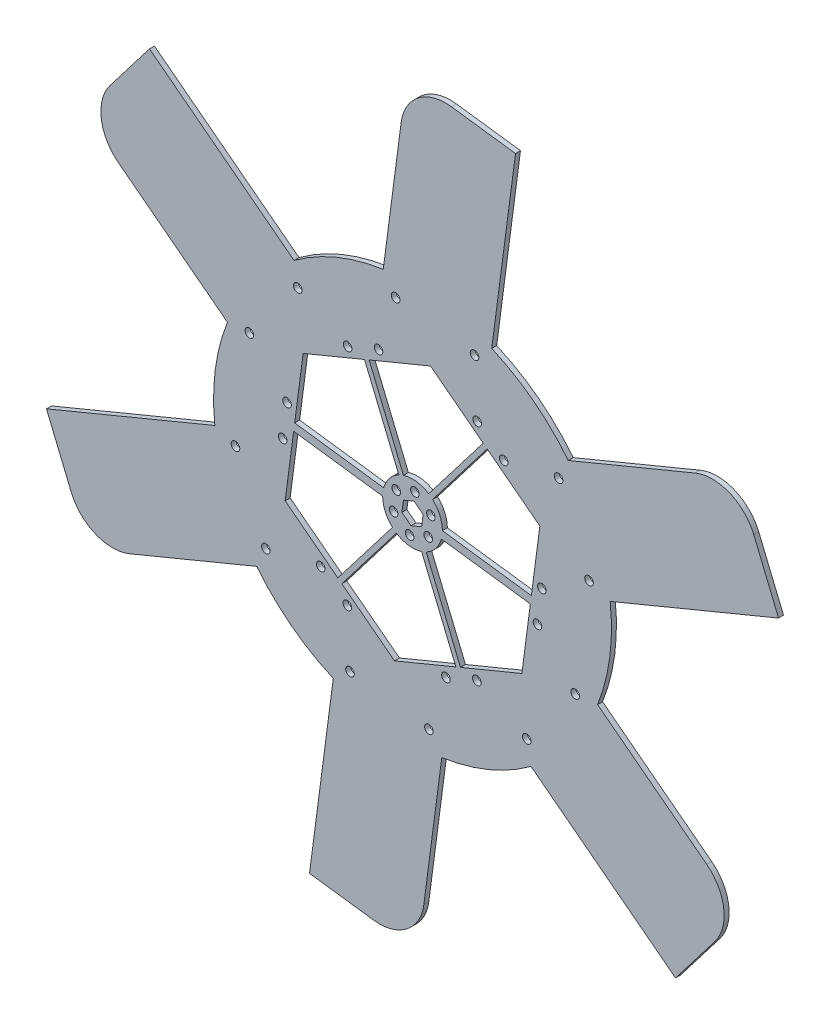
SolidWorks part; units mm, degrees
note: '?' marks a value the reader was unsure of.
material "6061 Alloy"
ref_plane "Front Plane" through (0, 0, 0) normal (0, 0, 1) x (1, 0, 0)
ref_plane "Top Plane" through (0, 0, 0) normal (0, 1, 0) x (1, 0, 0)
ref_plane "Right Plane" through (0, 0, 0) normal (1, 0, 0) x (0, 0, -1)
sketch "Sketch1" plane through (0, 0, 0) normal (0, 0, 1) x (1, 0, 0)
  circle A0 centre (0, 0) radius 127
  dimension "D1" = 254
extrude "Boss-Extrude1" add sketch "Sketch1" along normal blind 3.175
sketch "Sketch2" plane through (0, 0, 0) normal (0, 0, 1) x (1, 0, 0)
  line L0 (0, 0) -> (117.3327, 48.6008) construction
  circle A0 centre (0, 0) radius 82.55 construction
  circle A1 centre (0, 0) radius 114.3 construction
  point P0 (11.7333, 4.8601)
  point P5 (58.2494, 58.4937)
  point P6 (82.5498, -0.1727)
  point P7 (112.6792, 19.1805)
  point P8 (93.2389, 66.1136)
  dimension "D1" = 12.7
  dimension "D3" = 165.1
  dimension "D4" = 228.6
  dimension "D2" = 63.5
  dimension "D5" = 50.8
hole_wizard "M5 Clearance Hole1" positions "Sketch3" profile "Sketch4" hole size "M5" standard "ANSI Metric" end condition through all
sketch "Sketch3" plane through (0, 0, 0) normal (0, 0, -1) x (-1, 0, 0)
  point P0 (-58.2494, 58.4937)
  point P3 (-82.5498, -0.1727)
  point P6 (-93.2389, 66.1136)
  point P9 (-112.6792, 19.1805)
  point P12 (-11.7333, 4.8601)
sketch "Sketch4" plane through (58.2494, 58.4937, 0) normal (1, 0, 0) x (0, 1, 0)
  line L0 (0, 0) -> (0, 3.175)
  line L1 (0, 3.175) -> (2.75, 3.175)
  line L2 (2.75, 3.175) -> (2.75, 0)
  line L5 (2.75, 0) -> (0, 0)
  line L11 (0, -6.35) -> (0, 107.95) construction
  dimension "Thru Hole Dia." = 5.5
  dimension "Thru Hole Depth" = 3.175
ref_axis "Axis1" through (0, 0, -0.1588) along (0, 0, 1)?
pattern_circular "CirPattern1" count 6 over 360 about axis through (-0.1685, -0.0698, 0) along (0, 0, 1) of "M5 Clearance Hole1"
sketch "Sketch6" plane through (0, 0, 0) normal (0, 0, -1) x (-1, 0, 0)
  line L1 (-92.5275, 76.1287) -> (-180.5271, 112.5793)
  line L2 (-217.8621, 97.1146) -> (-233.6574, 58.9815)
  line L3 (-233.6574, 58.9815) -> (-119.258, 11.5957)
  line L4 (-119.258, 11.5957) -> (-92.5275, 76.1287)
  line L5 (0, 0) -> (-117.3327, 48.6008) construction
  arc A0 (-217.8621, 97.1146) -> (-180.5271, 112.5793) centre (-191.4622, 86.1795) cw
  dimension "D5" = 28.575
  dimension "D1" = 69.85
  dimension "D2" = 95.25
  dimension "D3" = 238.4425
  dimension "D4" = 34.925
extrude "Boss-Extrude2" add sketch "Sketch6" against normal up to surface (3.175 mm away) up to face at (39.9048, 69.1333, 3.175)
pattern_circular "CirPattern2" count 6 over 360 about axis through (0, 0, 0) along (0, 0, 1) of "Boss-Extrude2"
sketch "Sketch7" plane through (0, 0, 0) normal (0, 0, 1) x (1, 0, 0)
  line L2 (-30.6271, 69.7921) -> (-69.8057, 53.5638)
  line L3 (0, 0) -> (117.3327, 48.6008) construction
  line L10 (81.2905, 33.6716) -> (47.6471, 59.4871)
  line L11 (11.4848, 87.2354) -> (-27.6938, 71.0071)
  line L12 (-69.8057, 53.5638) -> (-75.2235, 12.4113)
  line L13 (-81.2905, -33.6716) -> (-47.6471, -59.4871)
  line L14 (-11.4848, -87.2354) -> (27.6938, -71.0071)
  line L15 (69.8057, -53.5638) -> (75.2235, -12.4113)
  line L16 (47.6471, 59.4871) -> (12.816, 14.0944)
  line L17 (45.1282, 61.4199) -> (10.2971, 16.0272)
  line L18 (-27.6938, 71.0071) -> (-5.7981, 18.1462)
  line L19 (-30.6271, 69.7921) -> (-8.7314, 16.9312)
  line L20 (-75.2235, 12.4113) -> (-18.4009, 4.9305)
  line L21 (-75.8727, 7.4808) -> (-19.05, 0)
  line L22 (-47.6471, -59.4871) -> (-12.816, -14.0944)
  line L23 (-10.2971, -16.0272) -> (-45.1282, -61.4199)
  line L24 (27.6938, -71.0071) -> (5.7981, -18.1462)
  line L25 (30.6271, -69.7921) -> (8.7314, -16.9312)
  line L26 (75.2235, -12.4113) -> (18.4009, -4.9305)
  line L27 (75.8727, -7.4808) -> (19.05, 0)
  line L28 (-75.8727, 7.4808) -> (-81.2905, -33.6716)
  line L29 (-45.1282, -61.4199) -> (-11.4848, -87.2354)
  line L30 (30.6271, -69.7921) -> (69.8057, -53.5638)
  line L31 (75.8727, -7.4808) -> (81.2905, 33.6716)
  line L32 (45.1282, 61.4199) -> (11.4848, 87.2354)
  arc A1 (-10.2971, -16.0272) -> (5.7981, -18.1462) centre (0, 0) ccw
  arc A2 (-30.6208, 69.7768) -> (-75.1833, 12.4061) centre (0, 0) ccw construction
  arc A3 (8.7314, -16.9312) -> (18.4009, -4.9305) centre (0, 0) ccw
  arc A4 (19.05, 0) -> (12.816, 14.0944) centre (0, 0) ccw
  arc A5 (10.2971, 16.0272) -> (-5.7981, 18.1462) centre (0, 0) ccw
  arc A6 (-8.7314, 16.9312) -> (-18.4009, 4.9305) centre (0, 0) ccw
  arc A7 (-19.05, 0) -> (-12.816, -14.0944) centre (0, 0) ccw
  arc A8 (-75.8324, 7.4755) -> (-47.637, -59.474) centre (0, 0) ccw construction
  arc A9 (-45.1181, -61.4068) -> (27.6875, -70.9919) centre (0, 0) ccw construction
  arc A10 (30.6208, -69.7768) -> (75.1833, -12.4061) centre (0, 0) ccw construction
  arc A11 (75.8324, -7.4755) -> (47.637, 59.474) centre (0, 0) ccw construction
  arc A12 (45.1181, 61.4068) -> (-27.6875, 70.9919) centre (0, 0) ccw construction
  dimension "D1" = 38.1
  dimension "D2" = 152.4
  dimension "D3" = 3.175
  dimension "D5" = 3.175
  dimension "D4" = 3.175
  dimension "D6" = 3.175
extrude "Cut-Extrude1" cut sketch "Sketch7" along normal up to next
sketch "Sketch13" plane through (0, 0, 0) normal (0, 1, 0) x (1, 0, 0)
  line L1 (-1.5875, 0) -> (1.5875, 0)
  line L2 (-1.5875, 0) -> (-1.5875, -3.175)
  line L3 (-1.5875, -3.175) -> (1.5875, -3.175)
  line L4 (1.5875, 0) -> (1.5875, -3.175)
  dimension "D1" = 3.175
ref_plane "Plane1" through (0, 0, 0) normal (-0.3827, 0.9239, 0) x (0.9239, 0.3827, 0)
sketch "Sketch14" plane through (0, 0, 0) normal (-0.3827, 0.9239, 0) x (0.9239, 0.3827, 0)
  line L0 (1.5875, -3.175) -> (-1.5875, -3.175)
  line L1 (-30.8058, -3.175) -> (30.8058, -3.175) construction
  line L2 (-1.5875, -3.175) -> (-1.5875, 0)
  line L3 (-82.55, 0) -> (82.55, 0) construction
  line L4 (-1.5875, 0) -> (1.5875, 0)
  line L5 (0, 0) -> (127, 0) construction
  line L6 (1.5875, 0) -> (1.5875, -3.175)
  line L8 (0, 0.1588) -> (0, -3.3338) construction
  dimension "D1" = 3.175
  dimension "D2" = 1.5875
sketch "Sketch16" plane through (0, 0, 3.175) normal (0, 0, 1) x (1, 0, 0)
  line L0 (0, 0) -> (117.3327, 48.6008) construction
  line L7 (6.7742, 2.806) -> (0.9571, 7.2696)
  line L8 (0.9571, 7.2696) -> (-5.8171, 4.4637)
  line L9 (-5.8171, 4.4637) -> (-6.7742, -2.806)
  line L10 (-6.7742, -2.806) -> (-0.9571, -7.2696)
  line L11 (-0.9571, -7.2696) -> (5.8171, -4.4637)
  line L12 (5.8171, -4.4637) -> (6.7742, 2.806)
  circle A0 centre (0, 0) radius 6.35 construction
  dimension "D1" = 12.7
extrude "Cut-Extrude2" cut sketch "Sketch16" against normal through all
